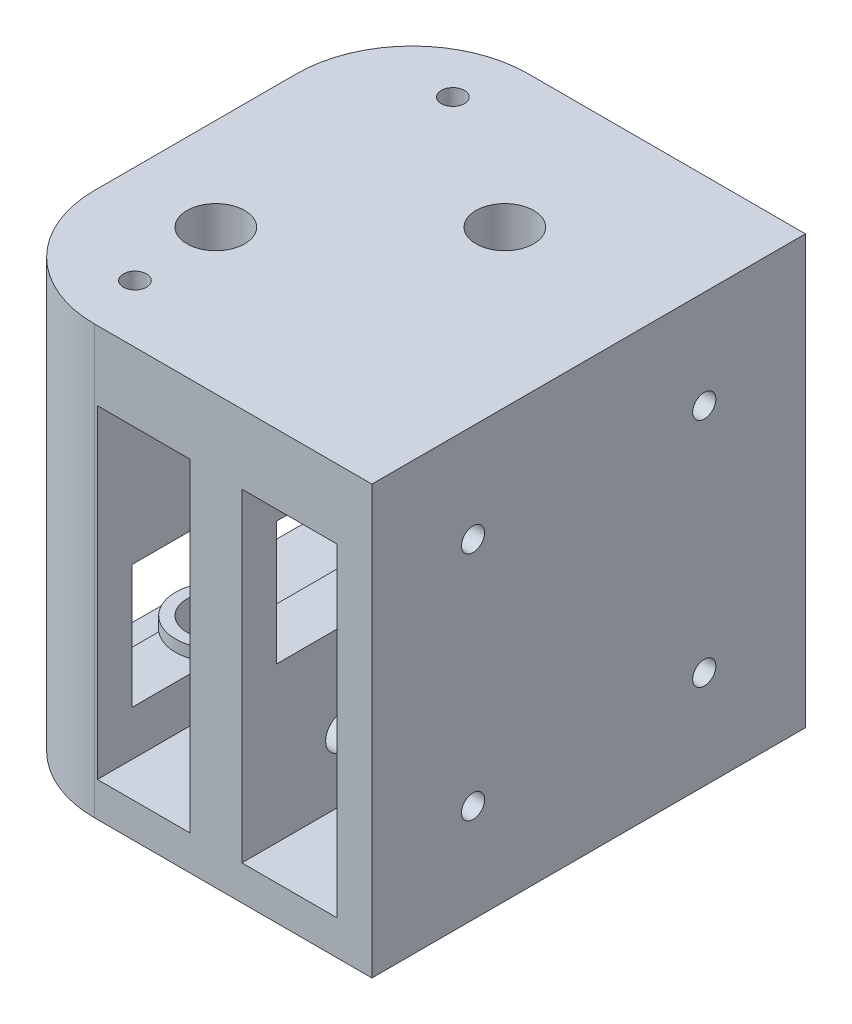
SolidWorks part; units mm, degrees
ref_plane "Front Plane" through (0, 0, 0) normal (0, 0, 1) x (1, 0, 0)
ref_plane "Top Plane" through (0, 0, 0) normal (0, 1, 0) x (1, 0, 0)
ref_plane "Right Plane" through (0, 0, 0) normal (1, 0, 0) x (0, 0, -1)
sketch "Top-Sketch1" plane through (0, 0, 0) normal (0, 1, 0) x (1, 0, 0)
  line L1 (0, 0) -> (34, 0)
  line L2 (0, 0) -> (0, 37.5)
  line L3 (0, 37.5) -> (34, 37.5)
  line L4 (34, 0) -> (34, 37.5)
  circle A0 centre (8.5, 32.5) radius 1
  circle A1 centre (8.5, 5) radius 1
  circle A2 centre (8, 12.5) radius 2.5
  circle A3 centre (20.5, 25) radius 2.5
  dimension "D3" = 5
  dimension "D5" = 2
  dimension "D1" = 13.5
  dimension "D2" = 12.5
  dimension "D4" = 12.5
  dimension "D6" = 8
  dimension "D8" = 12.5
  dimension "D9" = 5
  dimension "D10" = 5
  dimension "D11" = 37.5
  dimension "D12" = 12.5
  dimension "D7" = 25.5
extrude "Boss-Extrude4" add sketch "Top-Sketch1" along normal blind 6
sketch "TopRightRiser" plane through (0, 0, 0) normal (0, -1, 0) x (1, 0, 0)
  line L0 (5.75, -9.819) -> (5.75, 0)
  line L1 (0, 0) -> (34, 0) construction
  line L2 (5.75, 0) -> (10.25, 0)
  line L3 (10.25, 0) -> (10.25, -9.819)
  arc A0 (5.75, -9.819) -> (10.25, -9.819) centre (8, -12.5) ccw
  circle A1 centre (8, -12.5) radius 2.5 construction
  circle A2 centre (8, -12.5) radius 2.5
  point P13 (8, 0)
  dimension "D1" = 7
  dimension "D2" = 4.5
extrude "TopRightRiserBoss-Extrude5" add sketch "TopRightRiser" along normal blind 14.4
sketch "TopLeft" plane through (0, 0, 0) normal (0, -1, 0) x (1, 0, 0)
  line L0 (18.25, -22.319) -> (18.25, 0)
  line L1 (10.25, 0) -> (34, 0) construction
  line L2 (18.25, 0) -> (22.75, 0)
  line L3 (22.75, 0) -> (22.75, -22.319)
  line L4 (10.25, 0) -> (5.75, 0) construction
  circle A0 centre (20.5, -25) radius 2.5
  circle A1 centre (20.5, -25) radius 2.5 construction
  arc A2 (18.25, -22.319) -> (22.75, -22.319) centre (20.5, -25) ccw
  arc A3 (5.75, -9.819) -> (10.25, -9.819) centre (8, -12.5) ccw construction
  point P16 (20.5, 0)
extrude "TopLeftBoss-Extrude6" add sketch "TopLeft" along normal blind 4.9
sketch "MidWall" plane through (0, 0, 0) normal (0, -1, 0) x (-1, 0, 0)
  line L0 (-10.25, 9.819) -> (-10.25, 0) construction
  line L1 (0, 3) -> (-10.25, 3)
  line L2 (0, 3) -> (0, 0)
  line L3 (0, 0) -> (-10.25, 0)
  line L4 (-10.25, 3) -> (-10.25, 0)
  line L5 (0, 37.5) -> (0, 0) construction
  line L6 (-10.25, 0) -> (-5.75, 0) construction
  line L7 (-18.25, 0) -> (-18.25, 22.319) construction
  line L8 (-18.25, 0) -> (-22.75, 0)
  line L9 (-18.25, 0) -> (-18.25, 3)
  line L10 (-18.25, 3) -> (-22.75, 3)
  line L11 (-22.75, 0) -> (-22.75, 3)
  line L12 (-22.75, 22.319) -> (-22.75, 0) construction
  line L13 (-10.25, 0) -> (-18.25, 0) construction
  line L14 (-22.75, 0) -> (-34, 0) construction
  line L15 (-31, 0) -> (-34, 0)
  line L16 (-31, 0) -> (-31, 37.5)
  line L17 (-31, 37.5) -> (-34, 37.5)
  line L18 (-34, 0) -> (-34, 37.5)
  line L19 (-34, 37.5) -> (0, 37.5) construction
  line L20 (-34, 0) -> (-34, 37.5) construction
  dimension "D1" = 3
extrude "MidWallBoss-Extrude7" add sketch "MidWall" along normal blind 28
sketch "Bottom" plane through (0, -28, 0) normal (0, -1, 0) x (1, 0, 0)
  line L0 (0, 0) -> (34, 0) construction
  line L1 (0, 0) -> (34, 0)
  line L2 (0, 0) -> (0, -37.5)
  line L3 (0, -37.5) -> (34, -37.5)
  line L4 (34, 0) -> (34, -37.5)
  line L5 (34, 0) -> (34, -37.5) construction
  line L6 (0, -37.5) -> (0, 0) construction
extrude "BottomBoss-Extrude8" add sketch "Bottom" along normal blind 3
sketch "LowerRight" plane through (0, -28, 0) normal (0, 1, 0) x (1, 0, 0)
  line L0 (5.75, 9.819) -> (5.75, 3)
  line L1 (5.75, 3) -> (10.25, 3)
  line L2 (10.25, 3) -> (10.25, 9.819)
  line L6 (10.25, 9.819) -> (10.25, 3) construction
  line L7 (5.75, 3) -> (5.75, 9.819) construction
  line L8 (10.25, 3) -> (5.75, 3) construction
  circle A0 centre (8, 12.5) radius 2.5
  arc A1 (10.25, 9.819) -> (5.75, 9.819) centre (8, 12.5) ccw
  circle A2 centre (8, 12.5) radius 2.5 construction
  arc A3 (10.25, 9.819) -> (5.75, 9.819) centre (8, 12.5) ccw construction
extrude "LowerRightBoss-Extrude10" add sketch "LowerRight" along normal blind 4.9
sketch "LowerLeft" plane through (0, -28, 0) normal (0, 1, 0) x (1, 0, 0)
  line L1 (18.25, 0) -> (22.75, 0)
  line L5 (0, 0) -> (34, 0) construction
  line L6 (18.25, 22.319) -> (18.25, 0)
  line L7 (22.75, 22.319) -> (22.75, 0)
  circle A0 centre (20.5, 25) radius 2.5
  arc A1 (22.75, 22.319) -> (18.25, 22.319) centre (20.5, 25) ccw
  circle A2 centre (20.5, 25) radius 2.5 construction
  arc A3 (22.75, 22.319) -> (18.25, 22.319) centre (20.5, 25) ccw construction
  point P3 (20.5, 0)
  dimension "D1" = 4.5
extrude "LowerLeftBoss-Extrude9" add sketch "LowerLeft" along normal blind 14.4
fillet "Fillet1" radius 10 3 edges at (0, -12.5, 0) (0, -29.5, -37.5) (0, 3, -37.5)
sketch "LinearRailMountingHoles-Sketch10" plane through (34, 0, 0) normal (1, 0, 0) x (0, 0, -1)
  line L0 (0, 6) -> (37.5, 6) construction
  line L1 (37.5, 6) -> (37.5, -31) construction
  line L3 (37.5, -31) -> (0, -31) construction
  line L4 (0, 6) -> (0, -31) construction
  circle A0 centre (8.75, -2.5) radius 1
  circle A1 centre (8.75, -22.5) radius 1
  circle A2 centre (28.75, -22.5) radius 1
  circle A3 centre (28.75, -2.5) radius 1
  dimension "D7" = 2
  dimension "D1" = 8.5
  dimension "D2" = 20
  dimension "D3" = 20
  dimension "D4" = 8.75
  dimension "D5" = 8.5
  dimension "D6" = 8.75
extrude "LinearRailMountingHolesCut-Extrude1" cut sketch "LinearRailMountingHoles-Sketch10" against normal blind 3
sketch "TopRightInset-Sketch1" plane through (0, -14.4, 0) normal (0, -1, 0) x (1, 0, 0)
  line L0 (5.75, -9.819) -> (5.75, -3)
  line L1 (5.75, -3) -> (10.25, -3)
  line L2 (10.25, -3) -> (10.25, -9.819)
  line L3 (5.75, -9.819) -> (5.75, -3) construction
  line L4 (5.75, -3) -> (10.25, -3) construction
  line L5 (10.25, -3) -> (10.25, -9.819) construction
  arc A0 (10.25, -9.819) -> (5.75, -9.819) centre (8, -12.5) ccw
  arc A1 (5.75, -9.819) -> (10.25, -9.819) centre (8, -12.5) ccw construction
extrude "TopRightInset-Cut-Extrude1" cut sketch "TopRightInset-Sketch1" against normal blind 1
sketch "TopLeftInset-Sketch2" plane through (0, -4.9, 0) normal (0, -1, 0) x (1, 0, 0)
  line L0 (18.25, -22.319) -> (18.25, -3)
  line L1 (18.25, -3) -> (22.75, -3)
  line L2 (22.75, -3) -> (22.75, -22.319)
  line L3 (22.75, -3) -> (18.25, -3) construction
  line L4 (22.75, -22.319) -> (22.75, -3) construction
  line L5 (18.25, -22.319) -> (18.25, -3) construction
  arc A0 (22.75, -22.319) -> (18.25, -22.319) centre (20.5, -25) ccw
  arc A1 (18.25, -22.319) -> (22.75, -22.319) centre (20.5, -25) ccw construction
extrude "TopLeftInset-Cut-Extrude2" cut sketch "TopLeftInset-Sketch2" against normal blind 1
sketch "LowerLeftInset-Sketch3" plane through (0, -13.6, 0) normal (0, 1, 0) x (1, 0, 0)
  line L0 (18.25, 22.319) -> (18.25, 3)
  line L1 (18.25, 3) -> (22.75, 3)
  line L2 (22.75, 3) -> (22.75, 22.319)
  line L3 (22.75, 3) -> (18.25, 3) construction
  line L4 (18.25, 22.319) -> (18.25, 3) construction
  line L5 (22.75, 3) -> (22.75, 22.319) construction
  arc A0 (18.25, 22.319) -> (22.75, 22.319) centre (20.5, 25) ccw
  arc A1 (22.75, 22.319) -> (18.25, 22.319) centre (20.5, 25) ccw construction
extrude "LowerLeftInset-Cut-Extrude3" cut sketch "LowerLeftInset-Sketch3" against normal blind 1
sketch "LowerRightInset-Sketch4" plane through (0, -23.1, 0) normal (0, 1, 0) x (1, 0, 0)
  line L0 (5.75, 9.819) -> (5.75, 3)
  line L1 (5.75, 3) -> (10.25, 3)
  line L2 (10.25, 3) -> (10.25, 9.819)
  line L3 (10.25, 3) -> (5.75, 3) construction
  line L4 (5.75, 3) -> (5.75, 9.819) construction
  line L5 (10.25, 9.819) -> (10.25, 3) construction
  arc A0 (5.75, 9.819) -> (10.25, 9.819) centre (8, 12.5) ccw
  arc A1 (10.25, 9.819) -> (5.75, 9.819) centre (8, 12.5) ccw construction
extrude "LowerRightInsetCut-Extrude4" cut sketch "LowerRightInset-Sketch4" against normal blind 1
sketch "PushPinHoleSketch1" plane through (0, -31, 0) normal (0, -1, 0) x (1, 0, 0)
  circle A0 centre (20.5, -25) radius 1
  circle A1 centre (8, -12.5) radius 1
  circle A2 centre (8, -12.5) radius 2.5 construction
  circle A3 centre (20.5, -25) radius 2.5 construction
  dimension "D1" = 2
extrude "PushPinHoleCut-Extrude5" cut sketch "PushPinHoleSketch1" against normal through all
sketch "TopRightMountHoleAccessSketch2" plane through (5.75, 0, 0) normal (-1, 0, 0) x (0, 0, 1)
  circle A0 centre (-8.75, -2.5) radius 1.5
  dimension "D1" = 3
extrude "TopRightMountHoleAccessCut-Extrude2" cut sketch "TopRightMountHoleAccessSketch2" against normal blind 20 and the other way through all
sketch "BottomRightMountHoleAccessSketch3" plane through (18.25, 0, 0) normal (-1, 0, 0) x (0, 0, 1)
  circle A0 centre (-8.75, -22.5) radius 1.5
  arc A1 (-9.819, -3.5522) -> (-9.819, -1.4478) centre (-8.75, -2.5) ccw construction
extrude "BottomRightMountHoleAccessCut-Extrude3" cut sketch "BottomRightMountHoleAccessSketch3" against normal blind 5
equation "\"GABDepth\"= \"GABDistanceFromBackToFirstPulley\" + \"GABPulleyDDistanceBetween\" + \"GABDistanceFromPulleyToFront\""
equation "\"GABWidth\"= \"StandardWallThickness\" + \"GABDistanceFromLSideToPulley\" + \"GABPulleyWDistanceBetween\" + \"GABDistanceFromPulleyToRSide\""
equation "\"GABLowerHeight\"= 3mm"
equation "\"GABUpperHeight\"= 6mm"
equation "\"GABMidWallHeight\"= 28mm'Must equal 28 or changes alignment"
equation "\"StandardWallThickness\"= 3mm"
equation "\"GABMidShortRiserHeight\"= \"GABMidWallHeight\" / 2 - \"20TGT2PulleyWidth\"'Equals 5.3"
equation "\"LinearGBMountHolesXDistance\"= 20mm'Spec"
equation "\"GABHeight\"= \"GABLowerHeight\" + \"GABMidWallHeight\" + \"GABUpperHeight\""
equation "\"GBMountingHoleDiameter\"= 2mm"
equation "\"GABMidLongRiserHeight\"= \"GABMidWallHeight\" - \"GABMidShortRiserHeight\" - \"20TGT2PulleyWidth\"'Equals 14"
equation "\"GABLRClampHoleOffsetFromSide\"= 5mm"
equation "\"GABDistanceFromBackToFirstPulley\"= 13.5mm"
equation "\"GABPulleyDDistanceBetween\"= 12.5mm'From the100"
equation "\"GABPulleyWDistanceBetween\"= 14.5mm'From the100"
equation "\"GABDistanceFromPulleyToFront\"= 8mm"
equation "\"GABDistanceFromLSideToPulley\"= 9.5mm + \"StandardWallThickness\""
equation "\"GABDistanceFromPulleyToRSide\"= 7.5mm"
equation "\"GABDistanceToFrontClampHoles\"= 8.5mm"
equation "\"SteelShaft5mmHoleDiameter\"= 5mm"
equation "\"20TGT2PulleyWidth\"= 8.7mm'The STL of the Pulley in the diagram is a bit larger"
equation "\"7mmx1mmSpacerDiameter\"= 7mm"
equation "\"7mmx1mmSpacerHeight\"= 1mm"
equation "\"GABRiserBossOffset\"= 0.8mm'Aligns Pulleys"
equation "\"D1@Top-Sketch1\" = \"GABDistanceFromBackToFirstPulley\""
equation "\"D2@Top-Sketch1\" = \"GABPulleyDDistanceBetween\""
equation "\"D3@Top-Sketch1\" = \"SteelShaft5mmHoleDiameter\""
equation "\"D4@Top-Sketch1\" = \"GABPulleyDDistanceBetween\""
equation "\"D6@Top-Sketch1\" = \"GABDistanceFromPulleyToFront\""
equation "\"D8@Top-Sketch1\" = \"GABDistanceFromLSideToPulley\""
equation "\"D9@Top-Sketch1\" = \"GABLRClampHoleOffsetFromSide\""
equation "\"D10@Top-Sketch1\" = \"GABLRClampHoleOffsetFromSide\""
equation "\"D11@Top-Sketch1\" = \"GABWidth\""
equation "\"D1@Boss-Extrude4\"=\"GABUpperHeight\""
equation "\"D1@TopRightRiserBoss-Extrude5\" = \"GABMidLongRiserHeight\" + \"GABRiserBossOffset\" / 2"
equation "\"D1@TopLeftBoss-Extrude6\" = \"GABMidShortRiserHeight\" - \"GABRiserBossOffset\" / 2"
equation "\"D1@MidWall\" = \"StandardWallThickness\""
equation "\"D1@MidWallBoss-Extrude7\" = \"GABMidWallHeight\""
equation "\"D1@BottomBoss-Extrude8\" = \"GABLowerHeight\""
equation "\"D1@LowerLeftBoss-Extrude9\"=\"GABMidLongRiserHeight\" + \"GABRiserBossOffset\"/2"
equation "\"D1@LowerRightBoss-Extrude10\"=\"GABMidShortRiserHeight\" - \"GABRiserBossOffset\" / 2"
equation "\"D1@LinearRailMountingHoles-Sketch10\" =  ( \"GABHeight\" - \"LinearGBMountHolesXDistance\" )  / 2"
equation "\"D2@LinearRailMountingHoles-Sketch10\"=\"LinearGBMountHolesYDistance\""
equation "\"D3@LinearRailMountingHoles-Sketch10\" = \"LinearGBMountHolesXDistance\""
equation "\"D4@LinearRailMountingHoles-Sketch10\" =  ( \"GABWidth\" - \"LinearGBMountHolesXDistance\" )  / 2"
equation "\"D7@LinearRailMountingHoles-Sketch10\" = \"GBMountingHoleDiameter\""
equation "\"D1@LinearRailMountingHolesCut-Extrude1\" = \"StandardWallThickness\""
equation "\"D1@TopRightInset-Cut-Extrude1\" = \"7mmx1mmSpacerHeight\""
equation "\"D1@TopLeftInset-Cut-Extrude2\" = \"7mmx1mmSpacerHeight\""
equation "\"D1@LowerRightInsetCut-Extrude4\" = \"7mmx1mmSpacerHeight\""
equation "\"D1@TopRightRiser\"=\"7mmx1mmSpacerDiameter\""
equation "\"D7@Top-Sketch1\"=\"GABDepth\" - \"GABDistanceToFrontClampHoles\""
equation "\"LinearGBMountHolesYDistance\"= 20mm'Spec"
equation "\"D1@PushPinHoleSketch1\" = \"StealPinPushHoleDiameter\""
equation "\"StealPinPushHoleDiameter\"= 2mm"
